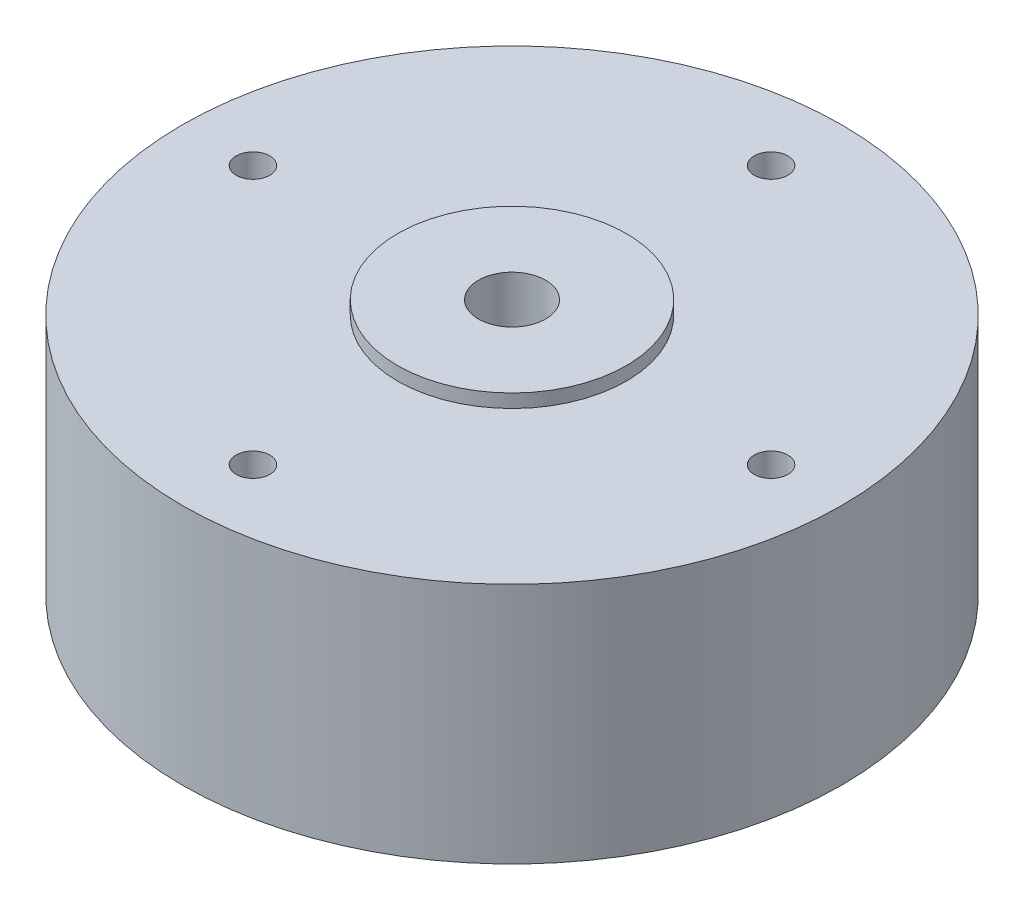
SolidWorks part; units mm, degrees
ref_plane "Front plane" through (0, 0, 0) normal (0, 0, 1) x (1, 0, 0)
ref_plane "Top plane" through (0, 0, 0) normal (0, 1, 0) x (1, 0, 0)
ref_plane "Right plane" through (0, 0, 0) normal (1, 0, 0) x (0, 0, -1)
ref_axis "Axis X" through (0, 0, 0) along (1, 0, 0)
ref_axis "Axis Y" through (0, 0, 0) along (0, 1, 0)
ref_axis "Axis Z" through (0, 0, 0) along (0, 0, 1)
sketch "Sketch1" plane through (0, 0, 0) normal (0, 1, 0) x (1, 0, 0)
  circle A0 centre (0, 0) radius 24.5
  dimension "D1" = 49
extrude "Extrude1" add sketch "Sketch1" along normal blind 19
sketch "Sketch2" plane through (0, 19, 0) normal (0, 1, 0) x (1, 0, 0)
  circle A0 centre (0, 0) radius 8.5
  circle A1 centre (0, 0) radius 24.5
  dimension "D1" = 49
  dimension "D2" = 17
extrude "Extrude2" cut sketch "Sketch2" against normal blind 1
sketch "Sketch3" plane through (0, 19, 0) normal (0, 1, 0) x (1, 0, 0)
  line L0 (0, 0) -> (0, 19.25) construction
  circle A0 centre (0, 0) radius 19.25 construction
  circle A1 centre (0, 19.25) radius 1.25
  circle A2 centre (19.25, 0) radius 1.25
  circle A3 centre (0, -19.25) radius 1.25
  circle A4 centre (-19.25, 0) radius 1.25
  dimension "D1" = 38.5
  dimension "D2" = 2.5
extrude "Extrude3" cut sketch "Sketch3" against normal blind 4
sketch "Sketch4" plane through (0, 0, 0) normal (0, -1, 0) x (1, 0, 0)
  line L0 (0, 0) -> (0, 12.5) construction
  circle A0 centre (0, 0) radius 12.5 construction
  circle A1 centre (0, 12.5) radius 1.5
  circle A2 centre (12.5, 0) radius 1.5
  circle A3 centre (0, -12.5) radius 1.5
  circle A4 centre (-12.5, 0) radius 1.5
  dimension "D1" = 3
  dimension "D3" = 25
  dimension "D2" = 4
extrude "Extrude4" cut sketch "Sketch4" against normal blind 3
chamfer "Chamfer1" [suppressed] distance 0.5 angle 45
sketch "Sketch6" plane through (0, 0, 0) normal (0, -1, 0) x (1, 0, 0)
  circle A0 centre (0, 0) radius 2.5
  dimension "D1" = 5
extrude "Extrude6" cut sketch "Sketch6" against normal through all
equation "\"motor_D\"= 49'Motor diameter"
equation "\"motor_H\"= 19'Motor heigh"
equation "\"motor_d1\"= 38.5'Seating diameter of screws on the fixed part of the motor"
equation "\"motor_s1\"= 2.5'Screws diameter on the fixed part of motor"
equation "\"motor_d2\"= 25'Seating diameter of screws on the moving part of the motor (if this parameter is not determine, write 0)"
equation "\"motor_s2\"= 3'Screws diameter on the moving part of motor"
equation "\"motor_Dc\"= 5'Central hole diameter of motor"
equation "\"bearing_d1\"= 6'Bearing inner diameter"
equation "\"bearing_d2\"= 17'Bearing external diameter"
equation "\"bearing h\"= 6'Bearing heigh"
equation "\"pin_d\"= 2'Pin diameter"
equation "\"pin_h\"= 13'Pin heigh"
equation "\"magnet_d1\"= 5'Magnet inner diameter"
equation "\"magnet_d2\"= 9.5'Magnet external diameter"
equation "\"magnet_h\"= 3'Magnet heigh"
equation "\"motor_a2\"= 0'Seating parameter in rectangle of screws on the moving part of the motor"
equation "\"motor_b2\"= 0'Seating parameter in rectangle of screws on the moving part of the motor"
equation "\"D1@Sketch1\"=\"motor_D\""
equation "\"D1@Extrude1\"=\"motor_H\""
equation "\"D1@Sketch2\"=\"motor_D\""
equation "\"motor_cmd\"= 17'Central magnet mount diameter"
equation "\"motor_cmh\"= 1'Central magnet mount heigh (if not write 0)"
equation "\"D2@Sketch2\"=\"motor_cmd\""
equation "\"D1@Extrude2\"= \"motor_cmh\""
equation "\"Extrude2\"= IIF ( \"motor_cmh\" = 0 , \"suppressed\" , \"unsuppressed\" )"
equation "\"D1@Sketch3\"=\"motor_d1\""
equation "\"D2@Sketch3\"=\"motor_s1\""
equation "\"D1@Extrude3\"=\"motor_cmh\"+3"
equation "\"D1@Sketch4\"=\"motor_s2\""
equation "\"D3@Sketch4\"=if( \"motor_d2\"=0,10,\"motor_d2\")"
equation "\"Extrude4\"= IIF ( \"motor_d2\" = 0 , \"suppressed\" , \"unsuppressed\" )"
equation "\"Extrude5\"= IIF ( \"motor_d2\" = 0 , \"unsuppressed\" , \"suppressed\" )"
equation "\"D1@Sketch6\"=\"motor_Dc\""
equation "\"motor_whR\"= 17'Distance from center of motor to wires"
equation "\"print_offset\"= 0.2'Offset for printing holes"
equation "\"ft_sensor_d1\"= 9.8"
equation "\"ft_sensor_d2\"= 24.9"
equation "\"ft_sensor_d3\"= 22.6'Inner diameter of "
equation "\"ft_sensor_h\"= 7.1"
equation "\"ft_sensor_whD\" = 5"
